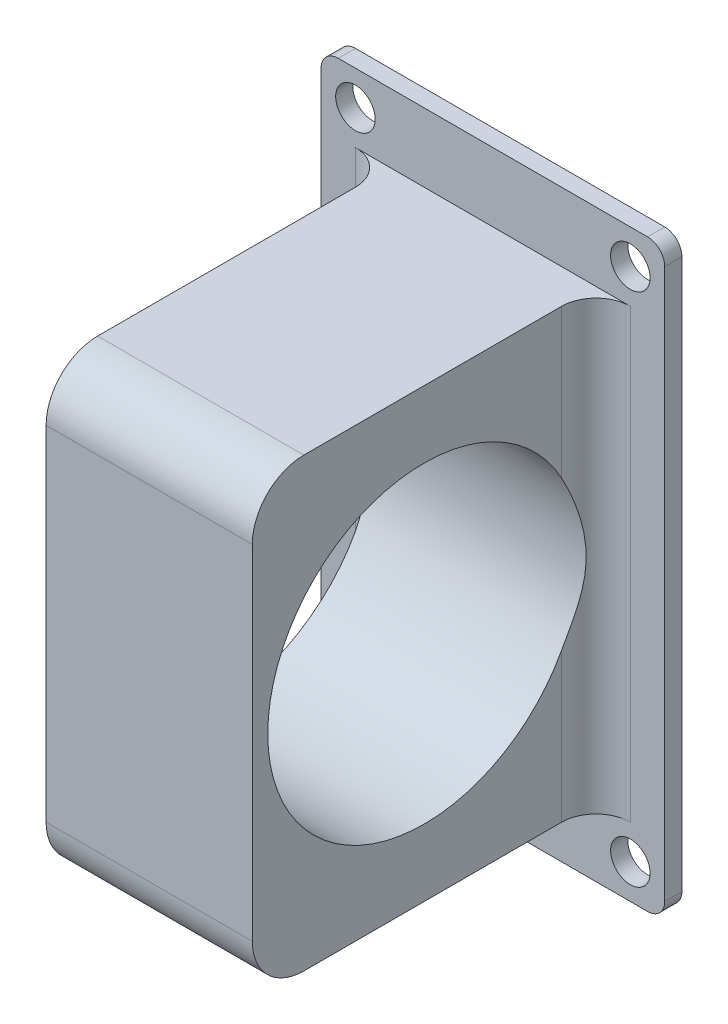
SolidWorks part; units mm, degrees
ref_plane "정면" through (0, 0, 0) normal (0, 0, 1) x (1, 0, 0)
ref_plane "윗면" through (0, 0, 0) normal (0, 1, 0) x (1, 0, 0)
ref_plane "우측면" through (0, 0, 0) normal (1, 0, 0) x (0, 0, -1)
sketch "스케치4" plane through (0, 0, 0) normal (0, 0, 1) x (1, 0, 0)
  line L0 (2, 2) -> (2, 32) construction
  line L1 (0, 0) -> (20, 0)
  line L2 (0, 0) -> (0, 34)
  line L3 (0, 34) -> (20, 34)
  line L4 (20, 0) -> (20, 34)
  line L5 (2, 32) -> (18, 32) construction
  line L6 (18, 2) -> (18, 32) construction
  line L7 (2, 2) -> (18, 2) construction
  circle A0 centre (2, 32) radius 1.15
  circle A1 centre (18, 32) radius 1.15
  circle A2 centre (2, 2) radius 1.15
  circle A3 centre (18, 2) radius 1.15
  dimension "D4" = 2.3
  dimension "D5" = 2.3
  dimension "D6" = 2.3
  dimension "D7" = 2.3
  dimension "D1" = 34
  dimension "D2" = 20
  dimension "D3" = 2
extrude "보스-돌출1" add sketch "스케치4" along normal blind 1
sketch "스케치5" plane through (0, 0, 1) normal (0, 0, 1) x (1, 0, 0)
  line L1 (4, 30) -> (16, 30)
  line L2 (4, 30) -> (4, 4)
  line L3 (4, 4) -> (16, 4)
  line L4 (16, 30) -> (16, 4)
  line L10 (4, 34) -> (4, 0)
  line L11 (4, 34) -> (4, 0) construction
  line L13 (16, 0) -> (16, 34)
  line L14 (16, 0) -> (16, 34) construction
  line L19 (20, 30) -> (0, 30)
  line L20 (20, 30) -> (0, 30) construction
  line L22 (0, 4) -> (20, 4)
  line L23 (0, 4) -> (20, 4) construction
  dimension "D1" = 4
  dimension "D2" = 4
  dimension "D3" = 4
  dimension "D4" = 4
extrude "보스-돌출2" add sketch "스케치5" along normal blind 20
sketch "스케치7" plane through (16, 0, 0) normal (1, 0, 0) x (0, 0, -1)
  line L1 (-21, 4) -> (-21, 30) construction
  line L4 (-21, 17) -> (-1, 17)
  line L5 (-21, 17) -> (-1, 17) construction
  circle A0 centre (-11, 17) radius 9.1
  dimension "D2" = 18.2
  dimension "D3" = 10
  dimension "D1" = 13
extrude "컷-돌출3" cut sketch "스케치7" against normal through all
fillet "필렛2" radius 3 1 edges at (10, 30, 21) type face fillet first side face at (10, 30, 11) second side face at (10, 17, 21)
fillet "필렛3" radius 3 1 edges at (10, 4, 21) type face fillet first side face at (10, 15.5, 21) second side face at (10, 4, 11)
fillet "필렛4" radius 1 1 edges at (20, 0, 0.5) type face fillet first side face at (10, 0, 0.5) second side face at (20, 17, 0.5)
fillet "필렛5" radius 1 1 edges at (0, 0, 0.5) type face fillet first side face at (0, 17, 0.5) second side face at (9.5, 0, 0.5)
fillet "필렛6" radius 1 1 edges at (0, 34, 0.5) type face fillet first side face at (0, 17.5, 0.5) second side face at (10, 34, 0.5)
fillet "필렛7" radius 1 1 edges at (20, 34, 0.5) type face fillet first side face at (20, 17.5, 0.5) second side face at (10.5, 34, 0.5)
fillet "필렛10" radius 2 1 edges at (4, 17, 1) type face fillet first side face at (4, 17, 1.9) second side face at (19.15, 2, 1)
fillet "필렛11" radius 2 1 edges at (16, 17, 1) type face fillet first side face at (16, 17, 1.9) second side face at (19.15, 2, 1)
